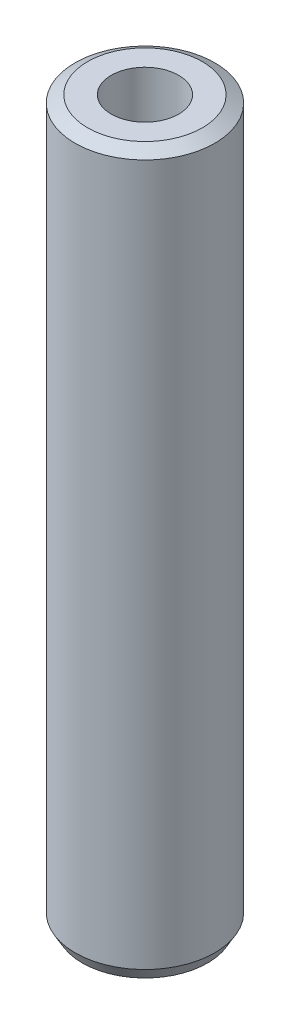
SolidWorks part; units mm, degrees
ref_plane "Front Plane" through (0, 0, 0) normal (0, 0, 1) x (1, 0, 0)
ref_plane "Top Plane" through (0, 0, 0) normal (0, 1, 0) x (1, 0, 0)
ref_plane "Right Plane" through (0, 0, 0) normal (1, 0, 0) x (0, 0, -1)
sketch "Sketch1" plane through (0, 0, 0) normal (0, 1, 0) x (1, 0, 0)
  circle A0 centre (0, 0) radius 35
  dimension "SHAFT_OD" = 70
extrude "Boss-Extrude1" add sketch "Sketch1" along normal blind 361.2801
sketch "Sketch2" plane through (0, 0, 0) normal (0, 1, 0) x (1, 0, 0)
  circle A0 centre (0, 0) radius 16.8919
  dimension "BORE_D" = 33.7839
extrude "Cut-Extrude1" cut sketch "Sketch2" along normal through all
chamfer "Chamfer1" distance 3.5993 angle 60 2 edges at (0, 361.2801, 35) (0, 0, 35) first distance on face at (0, 361.2801, 35) first distance on face at (0, 0, 16.8919)
